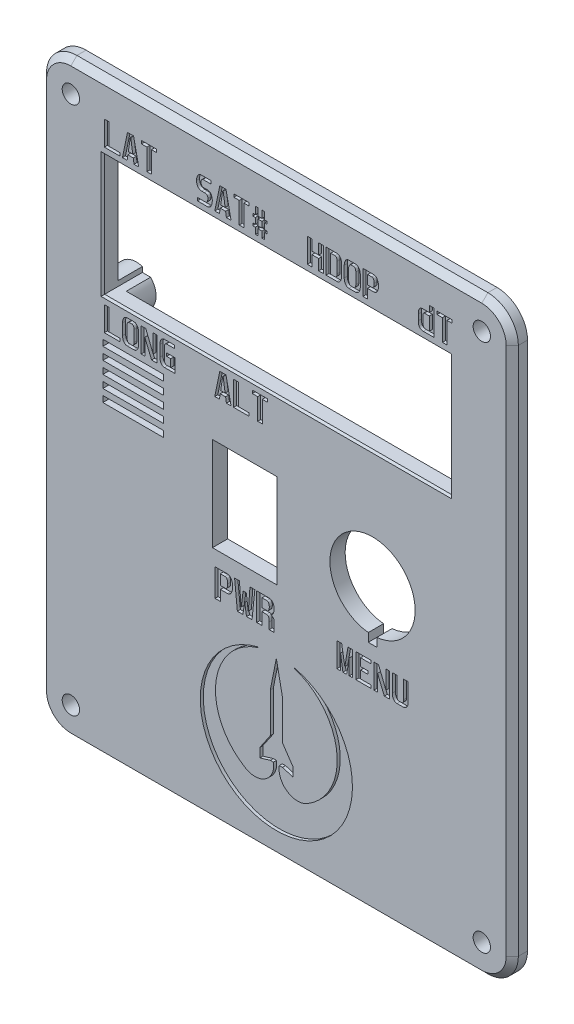
SolidWorks part; units mm, degrees
ref_plane "Front Plane" through (0, 0, 0) normal (0, 0, 1) x (1, 0, 0)
ref_plane "Top Plane" through (0, 0, 0) normal (0, 1, 0) x (1, 0, 0)
ref_plane "Right Plane" through (0, 0, 0) normal (1, 0, 0) x (0, 0, -1)
sketch "Sketch1" plane through (0, 0, 0) normal (0, 0, 1) x (1, 0, 0)
  line L0 (13.0175, 71.9455) -> (25.7175, 71.9455)
  line L1 (0, 123.063) -> (98.425, 123.063)
  line L2 (0, 123.063) -> (0, 0)
  line L3 (0, 0) -> (98.425, 0)
  line L4 (98.425, 123.063) -> (98.425, 0)
  line L5 (13.0175, 109.093) -> (85.4075, 109.093)
  line L6 (13.0175, 109.093) -> (13.0175, 83.693)
  line L7 (13.0175, 83.693) -> (85.4075, 83.693)
  line L8 (85.4075, 109.093) -> (85.4075, 83.693)
  line L9 (13.0175, 75.7555) -> (25.7175, 75.7555)
  line L10 (13.0175, 75.7555) -> (13.0175, 74.4855)
  line L11 (13.0175, 74.4855) -> (25.7175, 74.4855)
  line L12 (25.7175, 75.7555) -> (25.7175, 74.4855)
  line L13 (13.0175, 73.2155) -> (13.0175, 71.9455)
  line L14 (13.0175, 73.2155) -> (25.7175, 73.2155)
  line L15 (25.7175, 73.2155) -> (25.7175, 71.9455)
  line L16 (13.0175, 69.4055) -> (25.7175, 69.4055)
  line L17 (13.0175, 70.6755) -> (13.0175, 69.4055)
  line L18 (13.0175, 70.6755) -> (25.7175, 70.6755)
  line L19 (25.7175, 70.6755) -> (25.7175, 69.4055)
  line L20 (13.0175, 66.8655) -> (25.7175, 66.8655)
  line L21 (13.0175, 68.1355) -> (13.0175, 66.8655)
  line L22 (13.0175, 68.1355) -> (25.7175, 68.1355)
  line L23 (25.7175, 68.1355) -> (25.7175, 66.8655)
  line L24 (13.0175, 64.3255) -> (25.7175, 64.3255)
  line L25 (13.0175, 65.5955) -> (13.0175, 64.3255)
  line L26 (13.0175, 65.5955) -> (25.7175, 65.5955)
  line L27 (25.7175, 65.5955) -> (25.7175, 64.3255)
  line L28 (49.3395, 59.309) -> (98.425, 59.309) construction
  line L33 (49.2125, 109.093) -> (49.2125, 83.693) construction
  line L34 (35.8775, 69.088) -> (49.3395, 69.088)
  line L35 (35.8775, 69.088) -> (35.8775, 49.53)
  line L36 (35.8775, 49.53) -> (49.3395, 49.53)
  line L37 (49.3395, 69.088) -> (49.3395, 49.53)
  line L38 (85.4075, 83.693) -> (85.4075, 55.2047) construction
  line L39 (69.2785, 68.199) -> (69.2785, 49.53) construction
  line L40 (68.3895, 50.4636) -> (68.3895, 48.6856)
  line L41 (68.3895, 48.6856) -> (70.1675, 48.6856)
  line L42 (70.1675, 48.6856) -> (70.1675, 50.4636)
  line L43 (69.2785, 48.6856) -> (69.2785, 43.4273) construction
  line L44 (49.2125, 123.063) -> (49.2125, 0) construction
  arc A1 (70.1675, 50.4636) -> (68.3895, 50.4636) centre (69.2785, 59.309) ccw
  dimension "D18" = 17.78
  dimension "D1" = 72.39
  dimension "D2" = 25.4
  dimension "D3" = 98.425
  dimension "D4" = 36.195
  dimension "D5" = 13.97
  dimension "D6" = 1.27
  dimension "D7" = 12.7
  dimension "D8" = 7.9375
  dimension "D9" = 12.7
  dimension "D10" = 0
  dimension "D11" = 0
  dimension "D12" = 123.063
  dimension "D14" = 13.462
  dimension "D15" = 19.558
  dimension "D16" = 14.605
  dimension "D17" = 10.16
  dimension "D19" = 19.939
  dimension "D20" = 1.778
  dimension "D21" = 0.889
  dimension "D22" = 1.778
  dimension "D13" = 5
extrude "Boss-Extrude1" add sketch "Sketch1" along normal blind 3.175
sketch "Sketch2" plane through (0, 0, 0) normal (0, 0, -1) x (-1, 0, 0)
  line L0 (-85.4075, 96.393) -> (-13.0175, 96.393) construction
  line L1 (-85.4075, 83.693) -> (-85.4075, 109.093) construction
  line L2 (-13.0175, 109.093) -> (-13.0175, 83.693) construction
  line L3 (-49.2125, 109.093) -> (-49.2125, 83.693) construction
  line L4 (-85.4075, 109.093) -> (-13.0175, 109.093) construction
  line L5 (-13.0175, 83.693) -> (-85.4075, 83.693) construction
  circle A0 centre (-86.6775, 80.8355) radius 1.27
  circle A1 centre (-86.6775, 111.9505) radius 1.27
  circle A2 centre (-11.7475, 111.9505) radius 1.27
  circle A3 centre (-11.7475, 80.8355) radius 1.27
  circle A4 centre (-86.6775, 111.9505) radius 4.1275
  circle A5 centre (-86.6775, 80.8355) radius 4.1275
  circle A6 centre (-11.7475, 111.9505) radius 4.1275
  circle A7 centre (-11.7475, 80.8355) radius 4.1275
  dimension "D1" = 2.54
  dimension "D6" = 8.255
  dimension "D2" = 74.93
  dimension "D3" = 31.115
  dimension "D4" = 37.465
  dimension "D5" = 15.5575
extrude "Boss-Extrude2" add sketch "Sketch2" along normal blind 5.08
sketch "Sketch3" plane through (0, 0, -5.08) normal (0, 0, -1) x (-1, 0, 0)
  circle A0 centre (-86.6775, 111.9505) radius 1.27
  circle A1 centre (-86.6775, 80.8355) radius 1.27
  circle A2 centre (-11.7475, 80.8355) radius 1.27
  circle A3 centre (-11.7475, 111.9505) radius 1.27
  circle A4 centre (-86.6775, 111.9505) radius 1.27 construction
extrude "Cut-Extrude1" cut sketch "Sketch3" against normal blind 6.731
sketch "Sketch5" plane through (0, 0, 3.175) normal (0, 0, 1) x (1, 0, 0)
  line L0 (98.425, 123.063) -> (0, 123.063) construction
  line L1 (0, 123.063) -> (0, 0) construction
  line L4 (0, 123.063) -> (98.425, 123.063)
  line L5 (98.425, 123.063) -> (98.425, 0)
  line L6 (98.425, 0) -> (0, 0)
  line L7 (0, 0) -> (0, 123.063)
  circle A0 centre (6.35, 116.713) radius 6.35
  circle A1 centre (92.075, 116.713) radius 6.35
  circle A2 centre (92.075, 6.35) radius 6.35
  circle A3 centre (6.35, 6.35) radius 6.35
  circle A4 centre (6.35, 116.713) radius 1.8097
  circle A5 centre (92.075, 116.713) radius 1.8097
  circle A6 centre (92.075, 6.35) radius 1.8097
  circle A7 centre (6.35, 6.35) radius 1.8097
  line M39 (0, 123.063) -> (0, 0)
  line M40 (0, 0) -> (98.425, 0)
  line M41 (98.425, 0) -> (98.425, 123.063)
  line M42 (98.425, 123.063) -> (0, 123.063)
  dimension "D1" = 12.7
  dimension "D4" = 3.6195
  dimension "D2" = 6.35
  dimension "D3" = 6.35
  dimension "D5" = 6.35
  dimension "D6" = 6.35
extrude "Cut-Extrude2" cut sketch "Sketch5" against normal up to surface (3.175 mm away) contours A0 L4 M39 | A4 | A5 | A1 L5 M42 | A6 | A2 L6 M41 | A3 M39 M40 | A7 region at (1.4184, 121.6446, 3.175) region at (97.0066, 121.6446, 3.175) region at (1.4184, 1.4184, 3.175) region at (97.0066, 1.4184, 3.175) region at (6.35, 116.713, 3.175) region at (92.075, 116.713, 3.175) region at (92.075, 6.35, 3.175) region at (6.35, 6.35, 3.175) up to face at (49.2125, 96.393, 0)
sketch "Sketch7" plane through (0, 0, 3.175) normal (0, 0, 1) x (1, 0, 0)
  line L0 (35.8775, 49.53) -> (49.3395, 49.53) construction
  line L1 (35.8775, 40.64) -> (49.3395, 40.64) construction
  line L2 (215.1665, 573.3053) -> (1015.1665, 573.3053) construction
  line L3 (59.4995, 40.64) -> (79.0575, 40.64) construction
  line L4 (69.2785, 48.6856) -> (69.2785, 79.6211) construction
  line L5 (68.3895, 48.6856) -> (70.1675, 48.6856) construction
  line L6 (13.0175, 110.617) -> (85.4075, 110.617) construction
  line L7 (85.4075, 109.093) -> (13.0175, 109.093) construction
  line L8 (13.0175, 77.089) -> (80.772, 77.089) construction
  line L9 (13.0175, 83.693) -> (85.4075, 83.693) construction
  line L10 (49.2125, 33.6178) -> (49.2125, 83.693) construction
  text T0 "<b>PWR</b>" font "Unispace" height 5.715
  text T1 "<b>MENU</b>" font "Unispace" height 5.08
  text T2 "<b>LAT  SAT#  HDOP  dT</b>" font "Unispace" height 5.08
  text T3 "<b>LONG  ALT</b>" font "Unispace" height 5.08
  dimension "D1" = 13.462
  dimension "D2" = 8.89
  dimension "D3" = 19.558
  dimension "D4" = 9.779
  dimension "D5" = 72.39
  dimension "D6" = 1.524
  dimension "D7" = 6.604
extrude "Cut-Extrude3" cut sketch "Sketch7" against normal blind 0.635
sketch "Sketch8" plane through (0, 0, 3.175) normal (0, 0, 1) x (1, 0, 0)
  line L1 (13.0175, 109.093) -> (85.4075, 109.093)
  line L2 (13.0175, 109.093) -> (13.0175, 83.693)
  line L3 (13.0175, 83.693) -> (85.4075, 83.693)
  line L4 (85.4075, 109.093) -> (85.4075, 83.693)
extrude "Cut-Extrude4" cut sketch "Sketch8" against normal blind 25.4
sketch "Sketch9" plane through (0, 0, 0) normal (0, 0, -1) x (-1, 0, 0)
  line L0 (-49.2125, 123.063) -> (-49.2125, 0) construction
  line L1 (-92.075, 123.063) -> (-6.35, 123.063) construction
  line L2 (-6.35, 0) -> (-92.075, 0) construction
  line L3 (-98.425, 61.5315) -> (0, 61.5315) construction
  line L4 (-98.425, 6.35) -> (-98.425, 116.713) construction
  line L5 (0, 116.713) -> (0, 6.35) construction
  line L7 (-94.615, 99.6315) -> (-92.075, 99.6315)
  line L8 (-94.615, 99.6315) -> (-94.615, 23.4315)
  line L9 (-94.615, 23.4315) -> (-92.075, 23.4315)
  line L10 (-92.075, 99.6315) -> (-92.075, 23.4315)
  line L12 (-3.81, 99.6315) -> (-6.35, 99.6315)
  line L13 (-3.81, 99.6315) -> (-3.81, 23.4315)
  line L14 (-3.81, 23.4315) -> (-6.35, 23.4315)
  line L15 (-6.35, 99.6315) -> (-6.35, 23.4315)
  line L17 (-74.6125, 119.253) -> (-23.8125, 119.253)
  line L18 (-74.6125, 119.253) -> (-74.6125, 116.713)
  line L19 (-74.6125, 116.713) -> (-23.8125, 116.713)
  line L20 (-23.8125, 119.253) -> (-23.8125, 116.713)
  line L22 (-74.6125, 3.81) -> (-23.8125, 3.81)
  line L23 (-74.6125, 3.81) -> (-74.6125, 6.35)
  line L24 (-74.6125, 6.35) -> (-23.8125, 6.35)
  line L25 (-23.8125, 3.81) -> (-23.8125, 6.35)
  dimension "D1" = 76.2
  dimension "D2" = 76.2
  dimension "D3" = 38.1
  dimension "D4" = 2.54
  dimension "D5" = 38.1
  dimension "D6" = 2.54
  dimension "D7" = 50.8
  dimension "D8" = 25.4
  dimension "D9" = 2.54
  dimension "D10" = 50.8
  dimension "D11" = 25.4
  dimension "D12" = 2.54
  dimension "D13" = 3.81
  dimension "D14" = 3.81
  dimension "D15" = 3.81
  dimension "D16" = 3.81
extrude "Boss-Extrude4" add sketch "Sketch9" along normal blind 3.175
chamfer "Chamfer1" distance 1.27 angle 45 8 edges at (96.5651, 121.2031, 3.175) (49.2125, 123.063, 3.175) (1.8599, 121.2031, 3.175) (98.425, 61.5315, 3.175) (96.5651, 1.8599, 3.175) (49.2125, 0, 3.175) (1.8599, 1.8599, 3.175) (0, 61.5315, 3.175)
chamfer "Chamfer2" distance 0.635 angle 45 4 edges at (10.4775, 80.8355, -5.08) (10.4775, 111.9505, -5.08) (85.4075, 80.8355, -5.08) (85.4075, 111.9505, -5.08)
chamfer "Chamfer3" distance 0.381 angle 45 4 edges at (13.0175, 96.393, 3.175) (49.2125, 109.093, 3.175) (85.4075, 96.393, 3.175) (49.2125, 83.693, 3.175)
sketch "Sketch10" plane through (0, 0, 3.175) normal (0, 0, 1) x (1, 0, 0)
  line L0 (49.2125, 83.312) -> (49.2125, 17.145) construction
  line L1 (85.7885, 83.312) -> (12.6365, 83.312) construction
  line L2 (6.35, 1.27) -> (92.075, 1.27) construction
  line L3 (47.9425, 29.845) -> (49.2125, 36.195)
  line L5 (45.4025, 36.366) -> (45.4025, 36.245)
  line L7 (53.0225, 36.366) -> (53.0225, 36.245)
  line L9 (47.9425, 29.845) -> (47.9425, 21.59)
  line L10 (47.9425, 17.145) -> (48.5935, 17.145)
  line L11 (50.4825, 29.845) -> (50.4825, 21.59)
  line L12 (49.2125, 36.195) -> (50.4825, 29.845)
  line L13 (47.9425, 17.145) -> (45.7835, 16.51)
  line L14 (45.7835, 16.51) -> (45.7835, 18.415)
  line L15 (45.7835, 18.415) -> (47.9425, 21.59)
  line L16 (50.4825, 17.145) -> (52.6415, 16.51)
  line L17 (52.6415, 16.51) -> (52.6415, 18.415)
  line L18 (52.6415, 18.415) -> (50.4825, 21.59)
  line L19 (49.8315, 17.145) -> (50.4825, 17.145)
  line L20 (49.2125, 5.08) -> (49.2125, 1.27) construction
  arc A0 (45.4025, 36.366) -> (53.0225, 36.366) centre (49.2125, 20.955) ccw
  arc A1 (45.4025, 36.245) -> (42.8133, 13.16) centre (49.2125, 24.13) ccw
  arc A2 (42.8133, 13.16) -> (48.5935, 17.145) centre (44.7675, 16.51) ccw
  arc A3 (49.8315, 17.145) -> (55.6117, 13.16) centre (53.6575, 16.51) ccw
  arc A4 (55.6117, 13.16) -> (53.0225, 36.245) centre (49.2125, 24.13) ccw
  dimension "D1" = 31.75
  dimension "D3" = 25.4
  dimension "D2" = 19.685
  dimension "D4" = 2.54
  dimension "D5" = 3.81
  dimension "D6" = 1.27
  dimension "D7" = 12.7
  dimension "D8" = 2.54
  dimension "D9" = 6.35
  dimension "D10" = 2.159
  dimension "D11" = 2.159
  dimension "D12" = 0.635
  dimension "D13" = 1.905
  dimension "D14" = 3.175
  dimension "D15" = 3.175
  dimension "D16" = 3.175
  dimension "D17" = 12.065
  dimension "D18" = 1.2381
  dimension "D19" = 12.7983
  dimension "D20" = 7.0207
  dimension "D21" = 7.621
extrude "Cut-Extrude5" cut sketch "Sketch10" against normal blind 0.635
